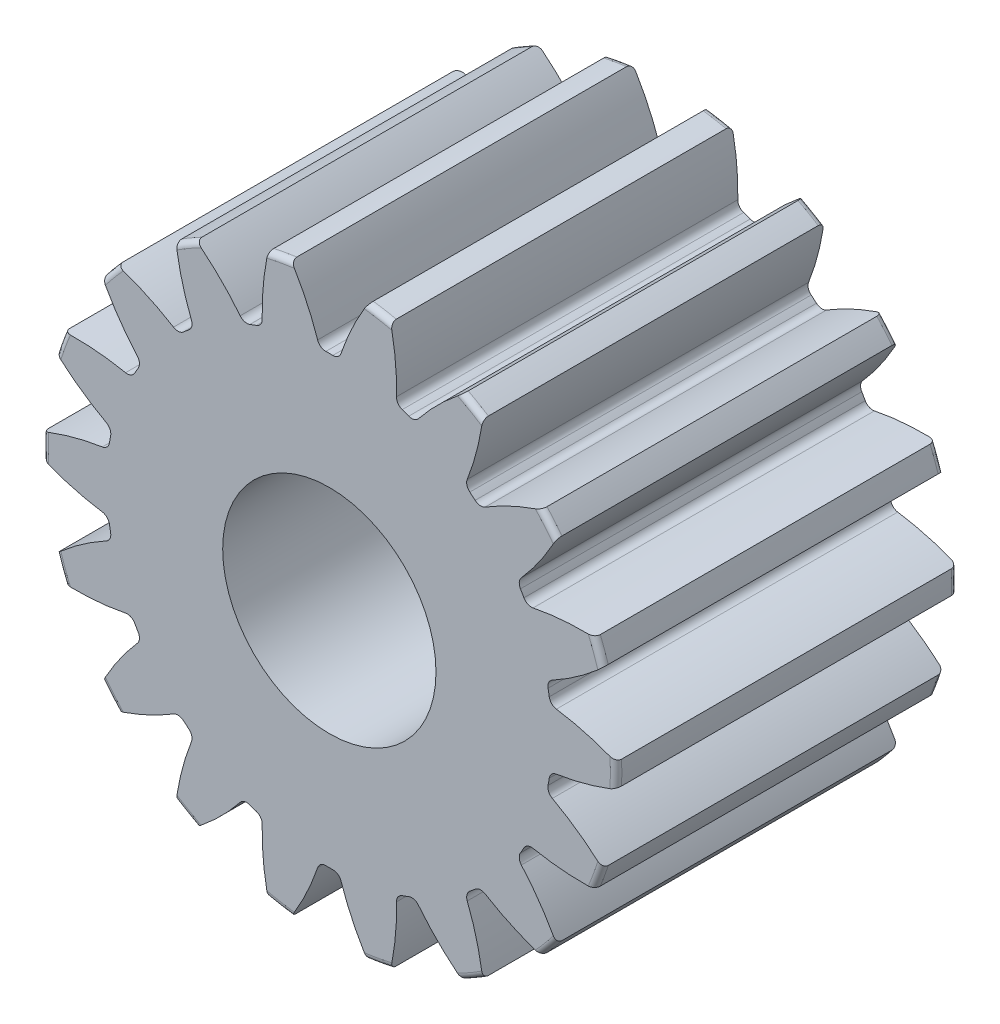
SolidWorks part; units mm, degrees
ref_plane "Front Plane" through (0, 0, 0) normal (0, 0, 1) x (1, 0, 0)
ref_plane "Top Plane" through (0, 0, 0) normal (0, 1, 0) x (1, 0, 0)
ref_plane "Right Plane" through (0, 0, 0) normal (1, 0, 0) x (0, 0, -1)
sketch "Sketch1" plane through (0, 0, 0) normal (0, 0, 1) x (1, 0, 0)
  line L0 (-228.6, 0) -> (228.6, 0) construction
  circle A0 centre (0, 0) radius 5.334 construction
  circle A1 centre (0, 0) radius 4.7625 construction
  circle A2 centre (0, 0) radius 4.1434 construction
  circle A3 centre (0, 0) radius 3.9751 construction
  circle A4 centre (0, 0) radius 1.9844 construction
  dimension "D2" = 0.5715
  dimension "D3" = 1.1906
  dimension "D1" = 1.1906
sketch "Sketch2" plane through (0, 0, 0) normal (1, 0, 0) x (0, 0, -1)
  line L0 (0, 0) -> (-3.175, 0) construction
  line L1 (-3.175, 0) -> (-9.525, 0) construction
  dimension "Overall Width" = 9.525
  dimension "Face Width" = 3.175
sketch "Sketch4" plane through (0, 0, 0) normal (1, 0, 0) x (0, 0, -1)
  line L0 (-9.525, 1.9844) -> (-9.525, 3.9751)
  line L1 (-9.525, 3.9751) -> (-6.35, 3.9751)
  line L2 (-6.35, 3.9751) -> (-6.35, 5.334)
  line L3 (-6.35, 5.334) -> (0, 5.334)
  line L4 (0, 5.334) -> (0, 1.9844)
  line L5 (-6.35, 3.9751) -> (-6.35, 0) construction
  line L6 (0, 5.334) -> (0, -5.334) construction
  line L7 (-6.35, 3.9751) -> (0, 3.9751) construction
  line L12 (-9.525, 1.9844) -> (0, 1.9844)
  dimension "D1" = 6.35
  dimension "D2" = 1.9844
revolve "Revolve1" add sketch "Sketch4" angle 360 about L1
fillet "Fillet2" radius 0.1067 4 edges at (0, 3.9751, 9.525) (0, 3.9751, 6.35) (0, 5.334, 6.35) (0, 5.334, 0)
sketch "Sketch7" plane through (0, 0, 6.35) normal (0, 0, 1) x (1, 0, 0)
  line L0 (0, 0) -> (0, 5.334) construction
  line L1 (0.4151, 4.7444) -> (0.6703, 5.2917) construction
  line L3 (0.9262, 5.253) -> (0.827, 4.6901) construction
  line L4 (0.827, 4.6901) -> (0.7195, 4.0804) construction
  line L5 (0, 0) -> (0.7195, 4.0804) construction
  line L6 (0.4151, 4.7444) -> (0, 0) construction
  line L7 (0.4151, 4.7444) -> (0.4649, 5.3137) construction
  line L8 (0.4151, 4.7444) -> (0, 0) construction
  circle A0 centre (0, 0) radius 5.334 construction
  arc A1 (-0.0648, 4.1429) -> (0.0648, 4.1429) centre (0, 0) cw
  circle A2 centre (0, 0) radius 4.1434 construction
  arc A3 (-0.4151, 4.7444) -> (0.4151, 4.7444) centre (0, 0) cw construction
  circle A4 centre (0, 0) radius 4.7625 construction
  arc A5 (1.139, 5.211) -> (0.712, 5.2863) centre (0, 0) ccw construction
  arc A6 (0.4151, 4.7444) -> (1.2326, 4.6002) centre (0, 0) cw construction
  arc A7 (-0.712, 5.2863) -> (0.712, 5.2863) centre (0, 0) cw
  arc A8 (0.2177, 4.251) -> (0.712, 5.2863) centre (4.7314, 2.7317) cw
  arc A9 (-0.2177, 4.251) -> (-0.712, 5.2863) centre (-4.7314, 2.7317) ccw
  arc A10 (-0.0648, 4.1429) -> (-0.2177, 4.251) centre (-0.0672, 4.3016) cw
  arc A11 (0.0648, 4.1429) -> (0.2177, 4.251) centre (0.0672, 4.3016) ccw
  point P26 (-0.1817, 4.1394)
  point P29 (0.1817, 4.1394)
  dimension "D4" = 0.1588
  dimension "D5" = 4.7625
  dimension "D3" = 20
  dimension "D1" = 1.6624
  dimension "D2" = 0.8312
extrude "Cut-Extrude2" cut sketch "Sketch7" against normal through all
pattern_circular "CirPattern1" count 18 over 360 about axis through (0, 0, 9.525) along (0, 0, -1) of "Cut-Extrude2"
sketch "Sketch8" plane through (0, 0, 0) normal (0, 1, 0) x (1, 0, 0)
  line L0 (-3.8684, -9.525) -> (3.8684, -9.525) construction
  line L1 (-4.0818, -6.35) -> (4.0818, -6.35)
  line L2 (-4.0818, -6.35) -> (-4.0818, -9.525)
  line L3 (-4.0818, -9.525) -> (4.0818, -9.525)
  line L4 (4.0818, -6.35) -> (4.0818, -9.525)
  line L5 (-4.0818, -6.35) -> (4.0818, -6.35) construction
  point P4 (0, -9.525)
extrude "Cut-Extrude3" cut sketch "Sketch8" against normal through all both and the other way through all
sketch "Sketch9" plane through (0, 0, 0) normal (0, 0, 1) x (1, 0, 0)
  circle A0 centre (0, 0) radius 4.7625
  circle A1 centre (0, 0) radius 4.7625 construction
equation "\"D1@Sketch1\"=2.25*(\"Pitch Dia.@Sketch1\"/\"Number of Teeth@Sketch1\")"
equation "\"D1@CirPattern1\"=\"Number of Teeth@Sketch1\""
equation "\"D1@Fillet2\"=\"OD@Sketch1\"*.01"
equation "\"D1@Sketch7\"=3.14159*(\"Pitch Dia.@Sketch1\"/\"Number of Teeth@Sketch1\")"
equation "\"D2@Sketch7\"=\"D1@Sketch7\"/2"
equation "\"D4@Sketch7\"=\"D1@Sketch7\"*.0955"
equation "\"D5@Sketch7\"=\"Pitch Dia.@Sketch1\"/2"
